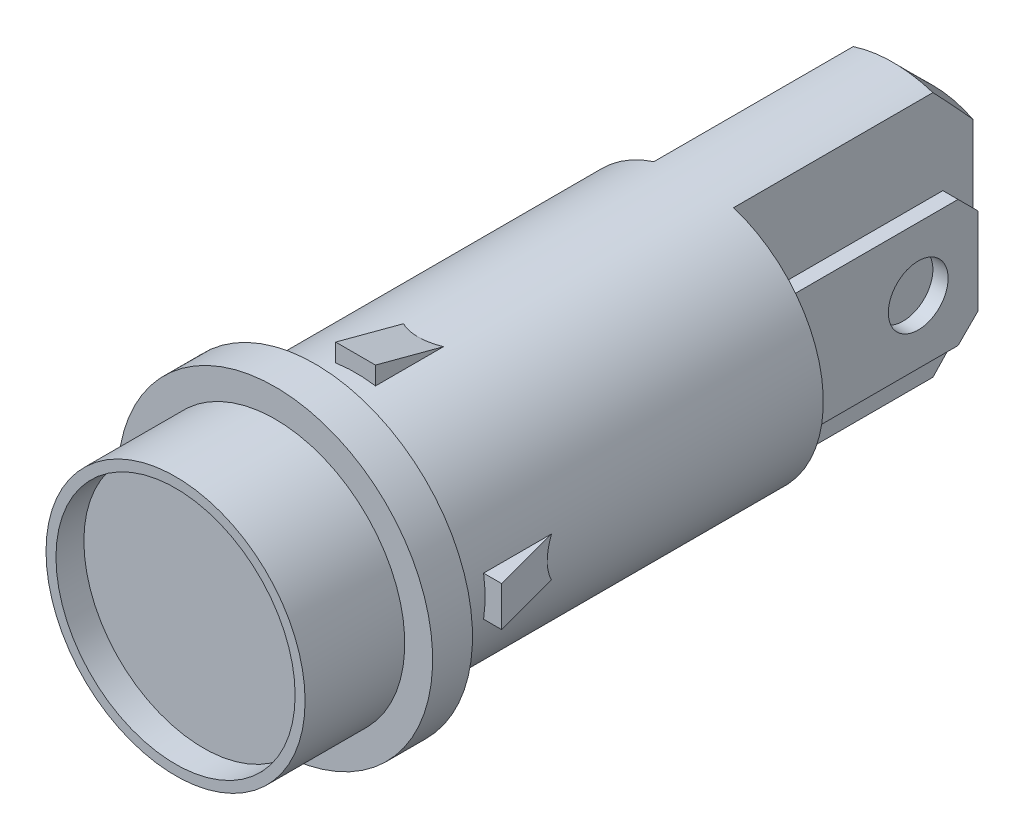
SolidWorks part; units mm, degrees
ref_plane "Front Plane" through (0, 0, 0) normal (0, 0, 1) x (1, 0, 0)
ref_plane "Top Plane" through (0, 0, 0) normal (0, 1, 0) x (1, 0, 0)
ref_plane "Right Plane" through (0, 0, 0) normal (1, 0, 0) x (0, 0, -1)
sketch "Sketch1" plane through (0, 0, 0) normal (0, 0, 1) x (1, 0, 0)
  circle A0 centre (0, 0) radius 6.5
  dimension "D1" = 13
extrude "Extrude1" add sketch "Sketch1" along normal blind 36.6
ref_plane "Plane1" through (0, 0, 31) normal (0, 0, 1) x (1, 0, 0)
sketch "Sketch2" plane through (0, 0, 31) normal (0, 0, -1) x (-1, 0, 0)
  circle A0 centre (0, 0) radius 7.9
  dimension "D1" = 15.8
extrude "Extrude2" add sketch "Sketch2" against normal blind 2
sketch "Sketch3" plane through (0, 0, 0) normal (0, 1, 0) x (1, 0, 0)
  line L0 (6.5, 0) -> (-6.5, 0) construction
  line L1 (2, 0) -> (6.5, 0)
  line L2 (2, 0) -> (2, -12)
  line L3 (2, -12) -> (6.5, -12)
  line L4 (6.5, 0) -> (6.5, -12)
  line L5 (6.5, -31) -> (6.5, 0) construction
  line L6 (0, 0) -> (0, 6.4201) construction
  line L7 (-6.5, 0) -> (-6.5, -12)
  line L8 (-2, -12) -> (-6.5, -12)
  line L9 (-2, 0) -> (-2, -12)
  line L10 (-2, 0) -> (-6.5, 0)
  dimension "D1" = 4
  dimension "D2" = 12
extrude "Cut-Extrude1" cut sketch "Sketch3" against normal through all and the other way through all
sketch "Sketch4" plane through (0, 0, 12) normal (0, 0, -1) x (-1, 0, 0)
  line L0 (-3.5, 0) -> (0, 0) construction
  line L1 (-4.262, 3.175) -> (-3.5, 3.175)
  line L2 (-4.262, 3.175) -> (-4.262, -3.175)
  line L3 (-4.262, -3.175) -> (-3.5, -3.175)
  line L4 (-3.5, 3.175) -> (-3.5, -3.175)
  dimension "D1" = 6.35
  dimension "D2" = 3.5
  dimension "D3" = 0.762
extrude "Extrude3" add sketch "Sketch4" along normal blind 10
chamfer "Chamfer1" distance 1 angle 45 2 edges at (3.881, -3.175, 2) (3.881, 3.175, 2)
sketch "Sketch5" plane through (4.262, 0, 0) normal (1, 0, 0) x (0, 0, -1)
  line L0 (-2, 0) -> (-5, 0) construction
  line L1 (-2, 2.175) -> (-2, -2.175) construction
  circle A0 centre (-5, 0) radius 1.5
  dimension "D1" = 3
  dimension "D2" = 3
extrude "Cut-Extrude2" cut sketch "Sketch5" against normal up to next
mirror "Mirror1" about plane through (0, 0, 0) normal (1, 0, 0) of "Extrude3", "Chamfer1", "Cut-Extrude2"
chamfer "Chamfer2" distance 2 angle 45 2 edges at (0, -6.5, 0) (0, 6.5, 0)
sketch "Sketch6" plane through (0, 0, 0) normal (0, 1, 0) x (1, 0, 0)
  line L0 (4.702, -19.0928) -> (7.3297, -28.968)
  line L1 (7.3297, -28.968) -> (4.702, -28.968)
  line L2 (4.702, -28.968) -> (4.702, -19.0928)
  line L4 (7.9, -31) -> (-7.9, -31) construction
  dimension "D1" = 2.032
extrude "Extrude4" add sketch "Sketch6" along normal mid plane 2
pattern_circular "CirPattern1" count 4 over 360 about axis through (0, 0, 36.6) along (0, 0, -1) of "Extrude4"
sketch "Sketch7" plane through (0, 0, 33) normal (0, 0, 1) x (1, 0, 0)
  circle A0 centre (0, 0) radius 6.5 construction
  circle A1 centre (0, 0) radius 6.5
extrude "Extrude-Thin1" add sketch "Sketch7" along normal blind 5 thin thin type one direction reverse wall 0.5
sketch "Sketch8" plane through (0, 0, 0) normal (0, 0, -1) x (-1, 0, 0)
  point P8 (0, 0)
other "CPoint1" parameters "Diameter"=2.54, "StubLength"=7
ref_axis "Axis1" through (0, 0, -10) along (0, 0, 1)
